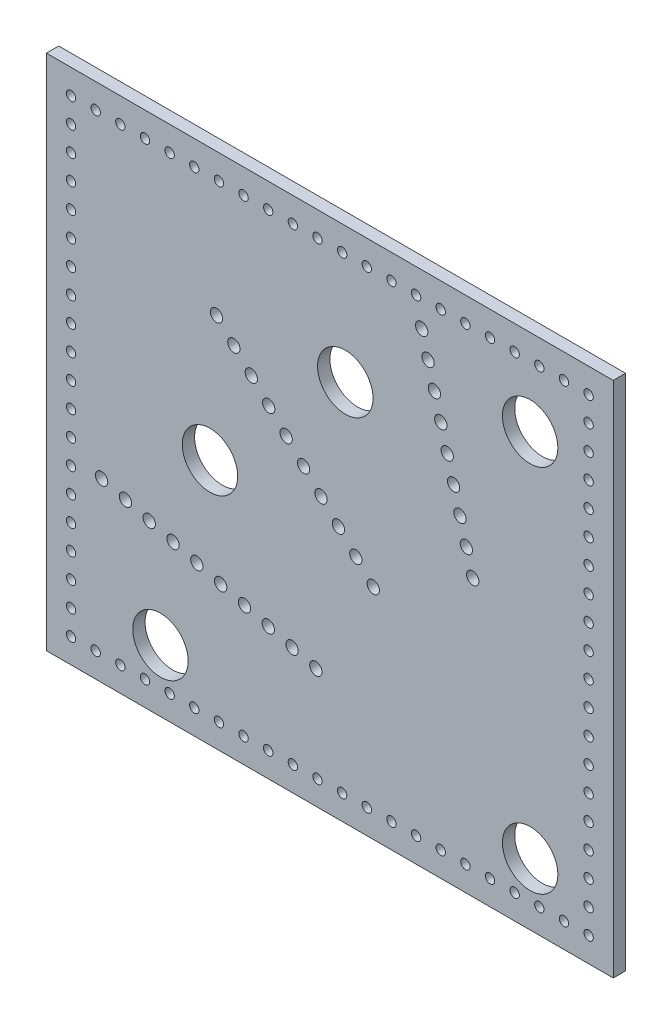
SolidWorks part; units mm, degrees
material "ABS PC"
ref_plane "Front Plane" through (0, 0, 0) normal (0, 0, 1) x (1, 0, 0)
ref_plane "Top Plane" through (0, 0, 0) normal (0, 1, 0) x (1, 0, 0)
ref_plane "Right Plane" through (0, 0, 0) normal (1, 0, 0) x (0, 0, -1)
sketch "Sketch1" plane through (0, 0, 0) normal (0, 0, 1) x (1, 0, 0)
  line L0 (-190.5, 0) -> (0, 0) construction
  line L1 (0, 0) -> (-164.9778, 95.25) construction
  line L2 (-95.25, 164.9778) -> (0, 0) construction
  line L3 (0, 0) -> (0, 190.5) construction
  line L4 (42.8422, -31.8767) -> (42.8422, 234.8233)
  line L5 (42.8422, -31.8767) -> (-249.2578, -31.8767)
  line L6 (42.8422, 234.8233) -> (-249.2578, 234.8233)
  line L7 (-249.2578, -31.8767) -> (-249.2578, 234.8233)
  circle A0 centre (0, 0) radius 14.2875
  circle A1 centre (-190.5, 0) radius 14.2875
  circle A2 centre (-164.9778, 95.25) radius 14.2875
  circle A3 centre (-95.25, 164.9778) radius 14.2875
  circle A4 centre (0, 190.5) radius 14.2875
  dimension "D1" = 28.575
  dimension "D2" = 28.575
  dimension "D3" = 28.575
  dimension "D4" = 28.575
  dimension "D5" = 28.575
  dimension "D6" = 190.5
  dimension "D7" = 190.5
  dimension "D8" = 190.5
  dimension "D9" = 190.5
  dimension "D10" = 30
  dimension "D11" = 30
  dimension "D12" = 30
  dimension "D13" = 266.7
  dimension "D14" = 292.1
extrude "I CAN CHANGE THESE NAMES?!" add sketch "Sketch1" along normal blind 6.35
sketch "Sketch2" plane through (0, 0, 6.35) normal (0, 0, 1) x (1, 0, 0)
  line L1 (42.8422, 234.8233) -> (-249.2578, 234.8233) construction
  line L2 (-249.2578, 234.8233) -> (-236.5578, 234.8233) construction
  line L3 (-249.2578, 234.8233) -> (-249.2578, -31.8767) construction
  line L4 (-249.2578, 222.1233) -> (42.8422, 222.1233) construction
  line L5 (42.8422, -31.8767) -> (42.8422, 234.8233) construction
  line L6 (-236.5578, 234.8233) -> (-236.5578, -31.8767) construction
  line L7 (-249.2578, -31.8767) -> (42.8422, -31.8767) construction
  line L8 (-236.5578, -31.8767) -> (-236.5578, -19.1767) construction
  line L9 (-236.5578, -19.1767) -> (42.8422, -19.1767) construction
  line L10 (42.8422, -19.1767) -> (30.1422, -19.1767) construction
  line L11 (30.1422, -19.1767) -> (30.1422, 222.1233) construction
  circle A0 centre (30.1422, 222.1233) radius 2.413
  circle A12 centre (30.1422, 209.4233) radius 2.413
  circle A13 centre (30.1422, 196.7233) radius 2.413
  circle A14 centre (30.1422, 184.0233) radius 2.413
  circle A15 centre (30.1422, 171.3233) radius 2.413
  circle A16 centre (30.1422, 158.6233) radius 2.413
  circle A17 centre (30.1422, 145.9233) radius 2.413
  circle A18 centre (30.1422, 133.2233) radius 2.413
  circle A19 centre (30.1422, 120.5233) radius 2.413
  circle A20 centre (30.1422, 107.8233) radius 2.413
  circle A21 centre (30.1422, 95.1233) radius 2.413
  circle A22 centre (30.1422, 82.4233) radius 2.413
  circle A23 centre (30.1422, 69.7233) radius 2.413
  circle A24 centre (30.1422, 57.0233) radius 2.413
  circle A25 centre (30.1422, 44.3233) radius 2.413
  circle A26 centre (30.1422, 31.6233) radius 2.413
  circle A27 centre (30.1422, 18.9233) radius 2.413
  circle A28 centre (30.1422, 6.2233) radius 2.413
  circle A29 centre (30.1422, -6.4767) radius 2.413
  circle A30 centre (30.1422, -19.1767) radius 2.413
  circle A32 centre (30.1422, -31.8767) radius 2.413 [skipped]
  circle A33 centre (17.4422, 222.1233) radius 2.413
  circle A34 centre (4.7422, 222.1233) radius 2.413
  circle A35 centre (-7.9578, 222.1233) radius 2.413
  circle A36 centre (-20.6578, 222.1233) radius 2.413
  circle A37 centre (-33.3578, 222.1233) radius 2.413
  circle A38 centre (-46.0578, 222.1233) radius 2.413
  circle A39 centre (-58.7578, 222.1233) radius 2.413
  circle A40 centre (-71.4578, 222.1233) radius 2.413
  circle A41 centre (-84.1578, 222.1233) radius 2.413
  circle A42 centre (-96.8578, 222.1233) radius 2.413
  circle A43 centre (-109.5578, 222.1233) radius 2.413
  circle A44 centre (-122.2578, 222.1233) radius 2.413
  circle A45 centre (-134.9578, 222.1233) radius 2.413
  circle A46 centre (-147.6578, 222.1233) radius 2.413
  circle A47 centre (-160.3578, 222.1233) radius 2.413
  circle A48 centre (-173.0578, 222.1233) radius 2.413
  circle A49 centre (-185.7578, 222.1233) radius 2.413
  circle A50 centre (-198.4578, 222.1233) radius 2.413
  circle A51 centre (-211.1578, 222.1233) radius 2.413
  circle A52 centre (-223.8578, 222.1233) radius 2.413
  circle A53 centre (-236.5578, 222.1233) radius 2.413
  circle A54 centre (-236.5578, 209.4233) radius 2.413
  circle A55 centre (-236.5578, 196.7233) radius 2.413
  circle A56 centre (-236.5578, 184.0233) radius 2.413
  circle A57 centre (-236.5578, 171.3233) radius 2.413
  circle A58 centre (-236.5578, 158.6233) radius 2.413
  circle A59 centre (-236.5578, 145.9233) radius 2.413
  circle A60 centre (-236.5578, 133.2233) radius 2.413
  circle A61 centre (-236.5578, 120.5233) radius 2.413
  circle A62 centre (-236.5578, 107.8233) radius 2.413
  circle A63 centre (-236.5578, 95.1233) radius 2.413
  circle A64 centre (-236.5578, 82.4233) radius 2.413
  circle A65 centre (-236.5578, 69.7233) radius 2.413
  circle A66 centre (-236.5578, 57.0233) radius 2.413
  circle A67 centre (-236.5578, 44.3233) radius 2.413
  circle A68 centre (-236.5578, 31.6233) radius 2.413
  circle A69 centre (-236.5578, 18.9233) radius 2.413
  circle A70 centre (-236.5578, 6.2233) radius 2.413
  circle A71 centre (-236.5578, -6.4767) radius 2.413
  circle A72 centre (-236.5578, -19.1767) radius 2.413
  circle A73 centre (-223.8578, -19.1767) radius 2.413
  circle A74 centre (-211.1578, -19.1767) radius 2.413
  circle A75 centre (-198.4578, -19.1767) radius 2.413
  circle A76 centre (-185.7578, -19.1767) radius 2.413
  circle A77 centre (-173.0578, -19.1767) radius 2.413
  circle A78 centre (-160.3578, -19.1767) radius 2.413
  circle A79 centre (-147.6578, -19.1767) radius 2.413
  circle A80 centre (-134.9578, -19.1767) radius 2.413
  circle A81 centre (-122.2578, -19.1767) radius 2.413
  circle A82 centre (-109.5578, -19.1767) radius 2.413
  circle A83 centre (-96.8578, -19.1767) radius 2.413
  circle A84 centre (-84.1578, -19.1767) radius 2.413
  circle A85 centre (-71.4578, -19.1767) radius 2.413
  circle A86 centre (-58.7578, -19.1767) radius 2.413
  circle A87 centre (-46.0578, -19.1767) radius 2.413
  circle A88 centre (-33.3578, -19.1767) radius 2.413
  circle A89 centre (-20.6578, -19.1767) radius 2.413
  circle A90 centre (-7.9578, -19.1767) radius 2.413
  circle A91 centre (4.7422, -19.1767) radius 2.413
  circle A92 centre (17.4422, -19.1767) radius 2.413
  circle A93 centre (30.1422, -19.1767) radius 2.413
  dimension "D5" = 4.826
  dimension "D1" = 12.7
  dimension "D2" = 12.7
  dimension "D3" = 12.7
  dimension "D4" = 12.7
  dimension "D7" = 21
  dimension "D6" = 22
  dimension "D8" = 20
  dimension "D9" = 22
extrude "NO WAY BRO" cut sketch "Sketch2" against normal blind 6.35 contours A0 | A38 | A37 | A36 | A35 | A34 | A33 | A12 | A13 | A14 | A43 | A42 | A41 | A40 | A39 | A15 | A16 | A17 | A18 | A19 | A20 | A21 | A22 | A23 | A24 | A25 | A26 | A27 | A28 | A29 | A30 | A50 | A49 | A48 | A47 | A46 | A45 | A44 | A58 | A57 | A56 | A55 | A54 | A53 | A52 | A51 | A66 | A65 | A64 | A63 | A62 | A61 | A60 | A59 | A74 | A73 | A72 | A71 | A70 | A69 | A68 | A67 | A82 | A81 | A80 | A79 | A78 | A77 | A76 | A75 | A90 | A89 | A88 | A87 | A86 | A85 | A84 | A83 | A92 | A91
sketch "Sketch5" plane through (0, 0, 6.35) normal (0, 0, 1) x (1, 0, 0)
  line L0 (0, 0) -> (-220.8106, 59.166) construction
  line L1 (0, 0) -> (-161.6446, 161.6446) construction
  line L2 (0, 0) -> (-55.879, 208.5434) construction
  line L3 (0, 190.5) -> (0, 0) construction
  line L4 (-95.25, 164.9778) -> (0, 0) construction
  line L5 (-190.5, 0) -> (0, 0) construction
  line L6 (-164.9778, 95.25) -> (0, 0) construction
  circle A0 centre (-161.6446, 161.6446) radius 3.175
  circle A1 centre (-55.879, 208.5434) radius 3.175
  circle A2 centre (-220.8106, 59.166) radius 3.175
  circle A3 centre (-208.5434, 55.879) radius 3.175
  circle A4 centre (-196.2761, 52.592) radius 3.175
  circle A5 centre (-184.0089, 49.305) radius 3.175
  circle A6 centre (-171.7416, 46.018) radius 3.175
  circle A7 centre (-159.4744, 42.731) radius 3.175
  circle A8 centre (-147.2071, 39.444) radius 3.175
  circle A9 centre (-134.9398, 36.157) radius 3.175
  circle A10 centre (-122.6726, 32.87) radius 3.175
  circle A11 centre (-110.4053, 29.583) radius 3.175
  circle A12 centre (-152.6644, 152.6644) radius 3.175
  circle A13 centre (-143.6841, 143.6841) radius 3.175
  circle A14 centre (-134.7038, 134.7038) radius 3.175
  circle A15 centre (-125.7236, 125.7236) radius 3.175
  circle A16 centre (-116.7433, 116.7433) radius 3.175
  circle A17 centre (-107.7631, 107.7631) radius 3.175
  circle A18 centre (-98.7828, 98.7828) radius 3.175
  circle A19 centre (-89.8026, 89.8026) radius 3.175
  circle A20 centre (-80.8223, 80.8223) radius 3.175
  circle A21 centre (-52.592, 196.2761) radius 3.175
  circle A22 centre (-49.305, 184.0089) radius 3.175
  circle A23 centre (-46.018, 171.7416) radius 3.175
  circle A24 centre (-42.731, 159.4744) radius 3.175
  circle A25 centre (-39.444, 147.2071) radius 3.175
  circle A26 centre (-36.157, 134.9398) radius 3.175
  circle A27 centre (-32.87, 122.6726) radius 3.175
  circle A28 centre (-29.583, 110.4053) radius 3.175
  dimension "D7" = 6.35
  dimension "D8" = 6.35
  dimension "D9" = 6.35
  dimension "D1" = 228.6
  dimension "D2" = 228.6
  dimension "D3" = 215.9
  dimension "D4" = 15
  dimension "D5" = 15
  dimension "D6" = 15
  dimension "D10" = 10
  dimension "D11" = 10
  dimension "D12" = 9
extrude "Cut-Extrude3" cut sketch "Sketch5" against normal blind 6.35
